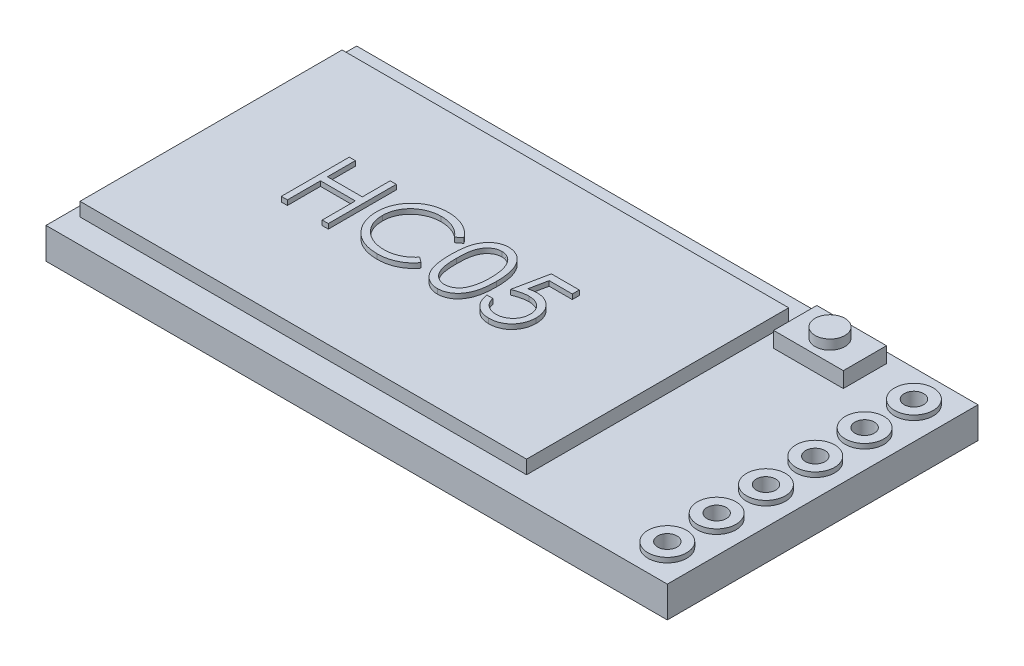
SolidWorks part; units mm, degrees
ref_plane "Front Plane" through (0, 0, 0) normal (0, 0, 1) x (1, 0, 0)
ref_plane "Top Plane" through (0, 0, 0) normal (0, 1, 0) x (1, 0, 0)
ref_plane "Right Plane" through (0, 0, 0) normal (1, 0, 0) x (0, 0, -1)
sketch "Sketch1" plane through (0, 0, 0) normal (0, 1, 0) x (1, 0, 0)
  line L1 (0, 0) -> (32, 0)
  line L2 (0, 0) -> (0, 16)
  line L3 (0, 16) -> (32, 16)
  line L4 (32, 0) -> (32, 16)
  line L5 (24.2196, 15.4779) -> (27.81, 15.4779)
  line L6 (24.2196, 15.4779) -> (24.2196, 13.2531)
  line L7 (24.2196, 13.2531) -> (27.81, 13.2531)
  line L8 (27.81, 15.4779) -> (27.81, 13.2531)
  line L9 (0.5, 14.75) -> (23.5, 14.75)
  line L10 (0.5, 14.75) -> (0.5, 1.25)
  line L11 (0.5, 1.25) -> (23.5, 1.25)
  line L12 (23.5, 14.75) -> (23.5, 1.25)
  circle A0 centre (30.35, 14.35) radius 0.5
  circle A1 centre (30.35, 14.35) radius 1
  circle A2 centre (30.35, 11.81) radius 0.5
  circle A3 centre (30.35, 11.81) radius 1
  circle A4 centre (30.35, 9.27) radius 0.5
  circle A5 centre (30.35, 9.27) radius 1
  circle A6 centre (30.35, 6.73) radius 0.5
  circle A7 centre (30.35, 6.73) radius 1
  circle A8 centre (30.35, 4.19) radius 0.5
  circle A9 centre (30.35, 4.19) radius 1
  circle A10 centre (30.35, 1.65) radius 0.5
  circle A11 centre (30.35, 1.65) radius 1
  dimension "D4" = 1
  dimension "D5" = 2
  dimension "D1" = 16
  dimension "D2" = 32
  dimension "D3" = 1.65
  dimension "D7" = 1.65
  dimension "D8" = 2.54
  dimension "D9" = 1.25
  dimension "D10" = 1.25
  dimension "D11" = 0.5
  dimension "D12" = 23
  dimension "D6" = 6
extrude "Boss-Extrude1" add sketch "Sketch1" along normal blind 1.6 contours L1 L4 L3 L2 A11 A9 A7 A5 A3 A1 L5 L8 L7 L6 L9 L12 L11 L10 region at (0.3578, 0, -8)
extrude "Boss-Extrude2" add sketch "Sketch1<3>" along normal blind 2.3 contours L12 L9 L10 L11 region at (12, 0, -8)
sketch "Sketch1<3>" plane through (0, 0, 0) normal (0, 1, 0) x (1, 0, 0) same geometry as "Sketch1"
extrude "Boss-Extrude3" add sketch "Sketch1<4>" along normal blind 2.4 contours L8 L5 L6 L7 region at (26.0148, 0, -14.3655)
sketch "Sketch1<4>" plane through (0, 0, 0) normal (0, 1, 0) x (1, 0, 0) same geometry as "Sketch1"
extrude "Boss-Extrude4" add sketch "Sketch1<5>" along normal blind 1.85 contours A11 A10 | A9 A8 | A7 A6 | A5 A4 | A3 A2 | A1 A0 region at (29.3783, 0, -14.35) region at (29.3783, 0, -11.81) region at (29.3783, 0, -9.27) region at (29.3783, 0, -6.73) region at (29.3783, 0, -4.19) region at (29.3783, 0, -1.65)
sketch "Sketch1<5>" plane through (0, 0, 0) normal (0, 1, 0) x (1, 0, 0) same geometry as "Sketch1"
sketch "Sketch2" plane through (0, 2.4, 0) normal (0, 1, 0) x (1, 0, 0)
  line L4 (27.81, 13.2531) -> (27.81, 15.4779)
  line L5 (27.81, 15.4779) -> (24.2196, 15.4779)
  line L6 (24.2196, 15.4779) -> (24.2196, 13.2531)
  line L7 (24.2196, 13.2531) -> (27.81, 13.2531)
  line L8 (27.81, 13.2531) -> (27.81, 15.4779)
  line L9 (27.81, 15.4779) -> (24.2196, 15.4779)
  line L10 (24.2196, 15.4779) -> (24.2196, 13.2531)
  line L11 (24.2196, 13.2531) -> (27.81, 13.2531)
  circle A0 centre (26.0158, 14.3631) radius 0.7667
  dimension "D2" = 1.7962
  dimension "D3" = 1.11
  dimension "D1" = 0
extrude "Boss-Extrude5" add sketch "Sketch2" along normal blind 0.5 contours A0 region at (26.0158, 2.4, -14.3631)
sketch "Sketch3" plane through (0, 2.3, 0) normal (0, 1, 0) x (1, 0, 0)
  text T0 "HC05"
  point P1 (0, 0)
extrude "Boss-Extrude6" add sketch "Sketch3" along normal blind 0.25
